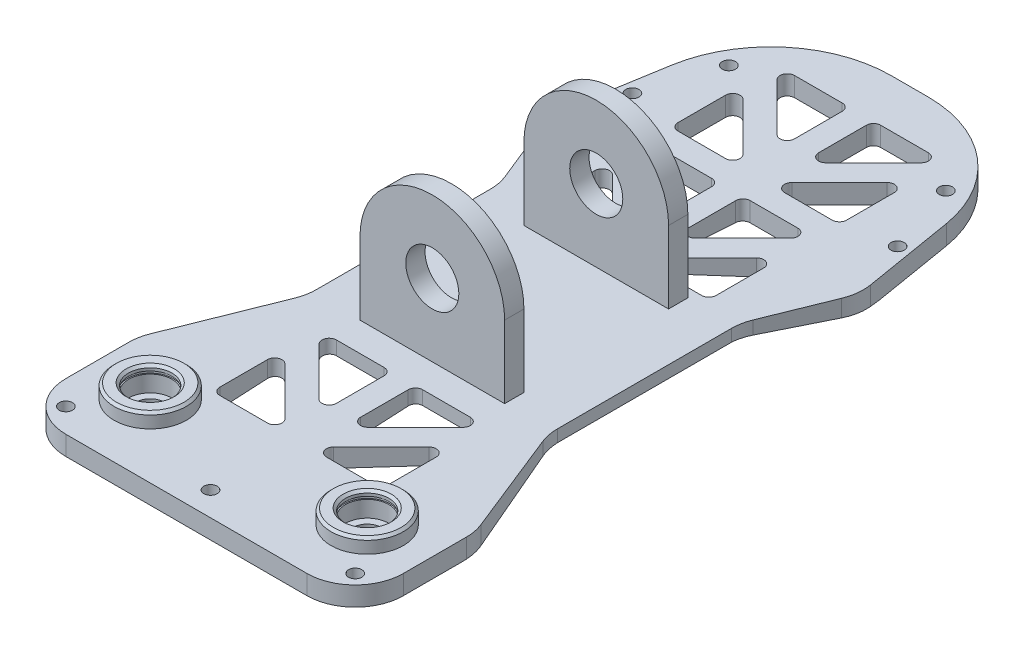
SolidWorks part; units mm, degrees
material "6061 合金"
ref_plane "前视基准面" through (0, 0, 0) normal (0, 0, 1) x (1, 0, 0)
ref_plane "上视基准面" through (0, 0, 0) normal (0, 1, 0) x (1, 0, 0)
ref_plane "右视基准面" through (0, 0, 0) normal (1, 0, 0) x (0, 0, -1)
other "Configuration Table"
sketch "草图1" plane through (0, 0, 0) normal (0, 1, 0) x (1, 0, 0)
  line L0 (0, 0) -> (0, 255.8207) construction
  line L1 (-70, 0) -> (70, 0)
  line L2 (70, 0) -> (70, 180)
  line L3 (70, 180) -> (50, 300)
  line L4 (50, 300) -> (-50, 300)
  line L5 (-70, 180) -> (-50, 300)
  line L6 (-70, 0) -> (-70, 180)
  point P8 (0, 300)
  dimension "D1" = 300
  dimension "D2" = 70
  dimension "D3" = 120
  dimension "D4" = 50
extrude "凸台-拉伸1" add sketch "草图1" along normal blind 8
sketch "草图2" plane through (70, 0, 0) normal (1, 0, 0) x (0, 0, -1)
  line L0 (40, 100) -> (40, -10.3339) construction
  line L1 (0, 8) -> (0, 0) construction
  line L2 (0, 8) -> (0, 58)
  line L3 (80, 8) -> (80, 58)
  arc A0 (80, 58) -> (0, 58) centre (40, 58) ccw
  circle A1 centre (40, 58) radius 10
  line M6 (180, 8) -> (0, 8)
  dimension "D3" = 20
  dimension "D1" = 40
  dimension "D2" = 50
extrude "凸台-拉伸2" [suppressed] add sketch "草图2" against normal up to surface (200 mm away) contours A0 L0 A1 L3 M6 | L0 A0 L2 A1 M6 up to face at (-70, 4, -90)
sketch "草图3" [suppressed] plane through (0, 10, 0) normal (0, 1, 0) x (1, 0, 0)
  line L0 (0, 0) -> (0, 135.8056) construction
  line L1 (-100, 0) -> (100, 0) construction
  line L2 (-70, 0) -> (70, 0)
  line L3 (-70, 0) -> (-70, 100)
  line L4 (-70, 100) -> (70, 100)
  line L5 (70, 0) -> (70, 100)
  line L6 (100, 0) -> (100, 80) construction
  line L7 (-100, 80) -> (-100, 0) construction
  dimension "D1" = 30
  dimension "D2" = 30
  dimension "D3" = 100
extrude "切除-拉伸1" [suppressed] cut sketch "草图3" along normal blind 171
sketch "草图4" plane through (0, 0, 0) normal (0, 0, 1) x (1, 0, 0)
  line L0 (0, 0) -> (0, 92.3322) construction
  line L1 (30, 38) -> (30, 8)
  line L2 (-30, 38) -> (-30, 8)
  line L3 (-70, 8) -> (70, 8) construction
  arc A0 (-30, 38) -> (30, 38) centre (0, 38) cw
  circle A1 centre (0, 38) radius 11
  line M10 (70, 8) -> (-70, 8)
  dimension "D2" = 30
  dimension "D3" = 22
  dimension "D1" = 30
extrude "凸台-拉伸3" add sketch "草图4" against normal blind 80 from offset 100 contours L0 L1 A0 A1 M10 | L0 A1 A0 L2 M10 region at (-15.2547, 34.8238, 0) region at (15.2547, 34.8238, 0) offset against normal yes
sketch "草图5" plane through (0, 8, 0) normal (0, 1, 0) x (1, 0, 0)
  line L0 (-47.074, 140) -> (51.1394, 140) construction
  line L1 (30, 180) -> (-30, 180) construction
  line L2 (30, 100) -> (-30, 100) construction
  line L3 (-30, 100) -> (30, 100) construction
  line L4 (-40, 170) -> (40, 170)
  line L5 (-40, 170) -> (-40, 110)
  line L6 (-40, 110) -> (40, 110)
  line L7 (40, 170) -> (40, 110)
  line L8 (30, 180) -> (30, 100) construction
  line L9 (-30, 180) -> (-30, 100) construction
  dimension "D1" = 10
  dimension "D2" = 10
  dimension "D3" = 10
  dimension "D4" = 10
extrude "切除-拉伸2" cut sketch "草图5" along normal blind 110 contours L7 L6 L5 L4
fillet "圆角1" radius 50 2 edges at (-50, 4, -300) (50, 4, -300)
fillet "圆角2" radius 200 2 edges at (-70, 4, -180) (70, 4, -180)
sketch "草图6" [suppressed] plane through (100, 0, 0) normal (1, 0, 0) x (0, 0, -1)
  line L0 (40, 60) -> (40, -52.2503) construction
  circle A0 centre (40, 60) radius 10 construction
  circle A1 centre (40, 60) radius 10 construction
  arc A2 (73.0468, 82.5368) -> (6.9532, 82.5368) centre (40, -25) ccw
  arc A3 (80, 60) -> (0, 60) centre (40, 60) ccw construction
  arc A4 (73.0468, 82.5368) -> (6.9532, 82.5368) centre (40, 60) ccw
  dimension "D2" = 225
  dimension "D1" = 25
extrude "切除-拉伸3" [suppressed] cut sketch "草图6" against normal through all both and the other way through all contours A2 A4
sketch "草图7" plane through (0, 8, 0) normal (0, 1, 0) x (1, 0, 0)
  line L0 (0, 0) -> (0, 141.3983) construction
  line L1 (-70, 0) -> (70, 0) construction
  line L2 (-136.8569, 140) -> (150.7223, 140) construction
  line L3 (-30, 170) -> (30, 170) construction
  line L4 (-30, 110) -> (30, 110) construction
  circle A0 centre (45, 30) radius 9
  dimension "D1" = 18
  dimension "D2" = 45
  dimension "D3" = 30
extrude "切除-拉伸6" cut sketch "草图7" against normal offset from surface (4 mm away) 4 contours A0 up to face at (0, 0, -185.4184)
sketch "草图10" plane through (0, 4, 0) normal (0, 1, 0) x (1, 0, 0)
  circle A0 centre (45, 30) radius 6
  dimension "D1" = 12
extrude "切除-拉伸7" cut sketch "草图10" against normal blind 28 contours A0
sketch "草图11" plane through (0, 8, 0) normal (0, 1, 0) x (1, 0, 0)
  circle A0 centre (45, 30) radius 12.5
  circle A1 centre (45, 30) radius 16.5
  dimension "D1" = 25
  dimension "D2" = 33
extrude "切除-拉伸8" [suppressed] cut sketch "草图11" against normal blind 5
sketch "草图12" plane through (0, 8, 0) normal (0, 1, 0) x (1, 0, 0)
  circle A0 centre (45, 30) radius 15
  dimension "D1" = 30
extrude "凸台-拉伸5" add sketch "草图12" along normal blind 6 contours A0
sketch "草图13" plane through (0, 14, 0) normal (0, 1, 0) x (1, 0, 0)
  circle A0 centre (45, 30) radius 9
  dimension "D1" = 18
extrude "切除-拉伸9" cut sketch "草图13" against normal blind 6
sketch "草图14" plane through (0, 14, 0) normal (0, 1, 0) x (1, 0, 0)
  circle A0 centre (45, 30) radius 9.5
  circle A2 centre (45, 30) radius 9 construction
  circle A3 centre (45, 30) radius 9
  circle M1 centre (45, 30) radius 9
  dimension "D1" = 19
extrude "卡簧槽" cut sketch "草图14" against normal blind 1.1 from offset 2.15 contours M1 | A0 region at (45, 14, -30) offset against normal yes
chamfer "倒角1" distance 1 angle 45 2 edges at (45, 14, -15) (45, 14, -21)
ref_plane "基准面1" through (0, 0, 0) normal (-1, 0, 0) x (0, 0, 1)
mirror "镜向1" about plane through (0, 0, 0) normal (-1, 0, 0) of "切除-拉伸6", "切除-拉伸7", "凸台-拉伸5", "切除-拉伸9", "卡簧槽", "倒角1"
sketch "草图16" plane through (0, 0, -100) normal (0, 0, 1) x (1, 0, 0)
  circle A0 centre (0, 38) radius 13
  dimension "D1" = 26
extrude "切除-拉伸10" [suppressed] cut sketch "草图16" against normal blind 0.75
sketch "草图17" plane through (0, 0, -180) normal (0, 0, -1) x (-1, 0, 0)
  circle A0 centre (0, 38) radius 13
  dimension "D1" = 26
extrude "切除-拉伸11" [suppressed] cut sketch "草图17" against normal blind 0.75 contours A0
sketch "草图18" plane through (-70, 0, 0) normal (-1, 0, 0) x (0, 0, 1)
  line L0 (-30, 92.2697) -> (-30, -20.0308) construction
  line L1 (-40, 8) -> (-40, 28)
  line L2 (-163.4475, 8) -> (0, 8) construction
  line L3 (-20, 28) -> (-20, 8)
  line L4 (-40, 8) -> (-20, 8)
  arc A0 (-20, 28) -> (-40, 28) centre (-30, 28) ccw
  circle A1 centre (-30, 28) radius 2.5
  dimension "D2" = 5
  dimension "D4" = 10
  dimension "D1" = 30
  dimension "D3" = 20
extrude "凸台-拉伸6" [suppressed] add sketch "草图18" against normal up to surface (200 mm away) contours A1 L0 | L0 A1 | L3 L4 L1 A0 up to face at (70, 4, -81.7237)
sketch "草图20" plane through (0, 8, 0) normal (0, 1, 0) x (1, 0, 0)
  line L0 (0, 0) -> (0, 309.5578) construction
  line L1 (-70, 0) -> (70, 0) construction
  line L2 (-60.0864, 49.2403) -> (-60.0864, 11.6041)
  line L3 (75.0864, 51.8093) -> (107.8414, 51.8093)
  line L4 (75.0864, 51.8093) -> (75.0864, 7.1083)
  line L5 (75.0864, 7.1083) -> (107.8414, 7.1083)
  line L6 (107.8414, 51.8093) -> (107.8414, 7.1083)
  line L7 (15, 49.2403) -> (60.0864, 49.2403)
  line L8 (15, 49.2403) -> (15, 11.6041)
  line L9 (15, 11.6041) -> (60.0864, 11.6041)
  line L10 (60.0864, 49.2403) -> (60.0864, 11.6041)
  line L11 (-15, 11.6041) -> (-60.0864, 11.6041)
  line L12 (-15, 49.2403) -> (-15, 11.6041)
  line L13 (-15, 49.2403) -> (-60.0864, 49.2403)
  line L14 (-107.8414, 51.8093) -> (-107.8414, 7.1083)
  line L15 (-75.0864, 7.1083) -> (-107.8414, 7.1083)
  line L16 (-75.0864, 51.8093) -> (-75.0864, 7.1083)
  line L17 (-75.0864, 51.8093) -> (-107.8414, 51.8093)
  dimension "D1" = 15
  dimension "D2" = 15
extrude "切除-拉伸12" [suppressed] cut sketch "草图20" along normal through all
chamfer "倒角2" [suppressed] distance 30 distance2 60
chamfer "倒角3" [suppressed] distance 60 distance2 30
fillet "圆角3" [suppressed] radius 10
ref_plane "脚底板中心面" through (0, 0, 0) normal (-1, 0, 0) x (0, 0, 1)
ref_plane "基准面3" through (0, 0, -30) normal (0, 0, 1) x (1, 0, 0)
sketch "草图22" plane through (0, 0, -30) normal (0, 0, 1) x (1, 0, 0)
  line L0 (45, 18.5577) -> (45, -23.1228) construction
  line L1 (-45, 24.8334) -> (-45, -23.1228) construction
  line L2 (45, 0) -> (45, 4) construction
  line L3 (-45, 0) -> (-45, 4) construction
ref_plane "基准面4" through (-45, 0, 0) normal (-1, 0, 0) x (0, 0, 1)
other "移动面1" flip direction yes face at (11, 38, -180) face at (11, 38, -100) offset 2 parameters "D1"=2
sketch "草图24" plane through (0, 8, 0) normal (0, 1, 0) x (1, 0, 0)
  line L0 (0, 310.351) -> (0, -16.2567) construction
  line L1 (5, 90) -> (35, 90)
  line L2 (35, 90) -> (5, 60)
  line L3 (5, 60) -> (5, 90)
  line L4 (35, 75.8579) -> (5, 45.8579)
  line L5 (5, 45.8579) -> (35, 45.8579)
  line L6 (35, 45.8579) -> (35, 75.8579)
  line L7 (-70, 0) -> (70, 0) construction
  line L8 (-5, 45.8579) -> (-35, 45.8579)
  line L9 (-35, 75.8579) -> (-5, 45.8579)
  line L10 (-35, 45.8579) -> (-35, 75.8579)
  line L11 (-35, 90) -> (-5, 60)
  line L12 (-5, 90) -> (-35, 90)
  line L13 (-5, 60) -> (-5, 90)
  line L14 (5, 280) -> (35, 280)
  line L15 (35, 280) -> (5, 250)
  line L16 (5, 250) -> (5, 280)
  line L17 (35, 265.8579) -> (5, 235.8579)
  line L18 (5, 235.8579) -> (35, 235.8579)
  line L19 (35, 235.8579) -> (35, 265.8579)
  line L26 (5, 225.8579) -> (35, 225.8579)
  line L27 (35, 225.8579) -> (5, 195.8579)
  line L28 (5, 195.8579) -> (5, 225.8579)
  line L29 (35, 211.7157) -> (5, 181.7157)
  line L30 (5, 181.7157) -> (35, 181.7157)
  line L31 (35, 181.7157) -> (35, 211.7157)
  line L38 (-35, 181.7157) -> (-35, 211.7157)
  line L39 (-5, 181.7157) -> (-35, 181.7157)
  line L40 (-35, 211.7157) -> (-5, 181.7157)
  line L41 (-5, 195.8579) -> (-5, 225.8579)
  line L42 (-35, 225.8579) -> (-5, 195.8579)
  line L43 (-5, 225.8579) -> (-35, 225.8579)
  line L44 (-35, 235.8579) -> (-35, 265.8579)
  line L45 (-5, 235.8579) -> (-35, 235.8579)
  line L46 (-35, 265.8579) -> (-5, 235.8579)
  line L47 (-5, 250) -> (-5, 280)
  line L48 (-35, 280) -> (-5, 250)
  line L49 (-5, 280) -> (-35, 280)
  line L50 (7.6436, 300) -> (-7.6436, 300) construction
  circle A0 centre (45, 270) radius 2.75
  circle A1 centre (55, 240) radius 2.75
  circle A3 centre (60, 10) radius 2.75
  circle A4 centre (0, 10) radius 2.75
  circle A5 centre (-60, 10) radius 2.75
  circle A7 centre (-55, 240) radius 2.75
  circle A8 centre (-45, 270) radius 2.75
  dimension "D13" = 5.5
  dimension "D20" = 5.5
  dimension "D23" = 5.5
  dimension "D1" = 30
  dimension "D2" = 30
  dimension "D3" = 5
  dimension "D4" = 90
  dimension "D5" = 10
  dimension "D6" = 30
  dimension "D7" = 30
  dimension "D8" = 10
  dimension "D9" = 10
  dimension "D10" = 30
  dimension "D11" = 10
  dimension "D12" = 280
  dimension "D14" = 45
  dimension "D15" = 55
  dimension "D17" = 30
  dimension "D18" = 60
  dimension "D21" = 60
  dimension "D22" = 10
extrude "切除-拉伸13" cut sketch "草图24" against normal blind 40
fillet "圆角6" radius 3 36 edges at (35, 4, -45.8579) (5, 4, -45.8579) (35, 4, -75.8579) (35, 4, -90) (5, 4, -90) (5, 4, -60) (-35, 4, -90) (-5, 4, -90) (-5, 4, -60) (-5, 4, -45.8579) (-35, 4, -45.8579) (-35, 4, -75.8579) (-5, 4, -181.7157) (-35, 4, -181.7157) (-35, 4, -211.7157) (35, 4, -211.7157) (35, 4, -181.7157) (5, 4, -181.7157) (-35, 4, -225.8579) (-5, 4, -225.8579) (-5, 4, -195.8579) (5, 4, -195.8579) (5, 4, -225.8579) (35, 4, -225.8579) (35, 4, -265.8579) (35, 4, -235.8579) (5, 4, -235.8579) (-35, 4, -235.8579) (-5, 4, -235.8579) (-35, 4, -265.8579) (-35, 4, -280) (-5, 4, -280) (-5, 4, -250) (5, 4, -250) (5, 4, -280) (35, 4, -280)
sketch "草图25" plane through (0, 8, 0) normal (0, 1, 0) x (1, 0, 0)
  line L0 (0, 0) -> (0, 309.3326) construction
  line L1 (64.1667, 215) -> (50, 180)
  line L2 (67.2788, 196.3273) -> (56.9633, 258.2199) construction
  line L3 (50, 180) -> (50, 100)
  line L4 (50, 100) -> (70, 50)
  line L5 (70, 0) -> (70, 163.4475) construction
  line L6 (-70, 0) -> (70, 0) construction
  line L7 (70, 50) -> (70, 163.4475)
  line L8 (67.2788, 196.3273) -> (64.1667, 215)
  line L9 (-50, 100) -> (-70, 50)
  line L10 (-50, 180) -> (-50, 100)
  line L11 (-64.1667, 215) -> (-50, 180)
  line L12 (-67.2788, 196.3273) -> (-64.1667, 215)
  line L13 (-70, 50) -> (-70, 163.4475)
  arc A0 (70, 163.4475) -> (67.2788, 196.3273) centre (-130, 163.4475) ccw construction
  arc A1 (70, 163.4475) -> (67.2788, 196.3273) centre (-130, 163.4475) ccw
  arc A2 (-70, 163.4475) -> (-67.2788, 196.3273) centre (130, 163.4475) cw
  dimension "D1" = 20
  dimension "D2" = 50
  dimension "D3" = 100
  dimension "D4" = 80
  dimension "D5" = 215
extrude "切除-拉伸14" cut sketch "草图25" against normal blind 10
fillet "圆角7" radius 20 10 edges at (50, 4, -100) (70, 4, -50) (70, 4, 0) (-70, 4, 0) (-70, 4, -50) (-50, 4, -100) (-50, 4, -180) (-64.1667, 4, -215) (50, 4, -180) (64.1667, 4, -215)
sketch "草图26" plane through (0, 0, 0) normal (1, 0, 0) x (0, 0, -1)
  line L0 (45, 9.555) -> (45, -12.3909) construction
  line L1 (45, 8) -> (45, 13) construction
  line L2 (45, 0) -> (103.8516, 3)
  line L3 (20, 0) -> (46.1484, 0) construction
  line L4 (103.8516, 8) -> (103.8516, 0) construction
  line L5 (103.8516, 3) -> (176.1058, 3)
  line L6 (176.1058, 0) -> (176.1058, 8) construction
  line L7 (176.1058, 3) -> (225, 0)
  line L8 (220.5636, 0) -> (258.2199, 0) construction
  line L9 (176.1058, 0) -> (103.8516, 0) construction
  line L10 (46.1484, 0) -> (53.5762, 0) construction
  line L11 (45, 0) -> (225, 0)
  dimension "D1" = 3
  dimension "D2" = 180
extrude "切除-拉伸15" cut sketch "草图26" against normal through all both and the other way through all
